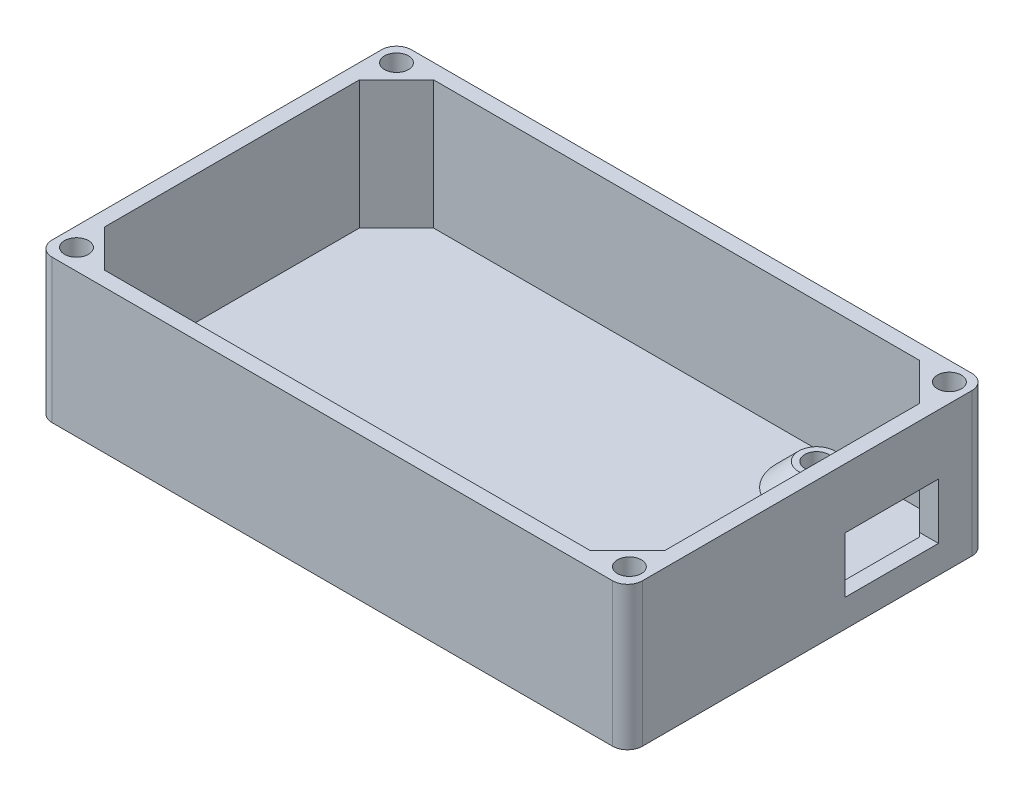
SolidWorks part; units mm, degrees
ref_plane "Front Plane" through (0, 0, 0) normal (0, 0, 1) x (1, 0, 0)
ref_plane "Top Plane" through (0, 0, 0) normal (0, 1, 0) x (1, 0, 0)
ref_plane "Right Plane" through (0, 0, 0) normal (1, 0, 0) x (0, 0, -1)
sketch "Sketch1" plane through (0, 0, 0) normal (0, 1, 0) x (1, 0, 0)
  line L0 (-1056.3053, 0) -> (48943.6947, 0) construction
  line L6 (27.9993, -24.5) -> (-50.8607, -24.5)
  line L8 (-7.0007, -998.7263) -> (-7.0007, 49001.2737) construction
  line L9 (27.9993, -24.5) -> (27.9993, 23.5)
  line L10 (27.9993, 23.5) -> (-50.8607, 23.5)
  line L11 (-50.8607, -24.5) -> (-50.8607, 23.5)
  line L12 (27.9993, -24.5) -> (-50.8607, 23.5) construction
  line L13 (27.9993, 23.5) -> (-50.8607, -24.5) construction
  point P0 (-7.0007, -0.5)
  dimension "D1" = 0.5
  dimension "D2" = 35
  dimension "D3" = 23.5
  dimension "D4" = 24.5
  dimension "D5" = 43.86
extrude "Boss-Extrude1" add sketch "Sketch1" along normal blind 18.15 and the other way blind 1
shell "Shell1" thickness 2 removed face at (-11.4307, 18.15, 0.5)
sketch "Sketch4" plane through (0, 1, 0) normal (0, 1, 0) x (1, 0, 0)
  line L0 (-50.8607, 23.5) -> (-50.8607, -24.5) construction
  line L1 (-50.8607, -24.5) -> (27.9993, -24.5) construction
  line L2 (27.9993, 23.5) -> (-50.8607, 23.5) construction
  circle A0 centre (-35.6907, -17.71) radius 2
  circle A1 centre (-4.7107, -11.75) radius 2
  circle A2 centre (11.6793, 17.1) radius 2
  dimension "D1" = 4
  dimension "D2" = 15.17
  dimension "D3" = 6.79
  dimension "D4" = 6.4
  dimension "D5" = 47.37
  dimension "D6" = 12.75
  dimension "D7" = 46.15
extrude "Boss-Extrude2" add sketch "Sketch4" against normal blind 4.4 from offset 3
chamfer "Chamfer2" distance 3.4 angle 45 1 edges at (-4.7107, 1, 13.75)
chamfer "Chamfer3" distance 3.4 angle 45 1 edges at (11.6793, 1, -15.1)
chamfer "Chamfer4" distance 3.4 angle 45 1 edges at (-35.6907, 1, 19.71)
sketch "Sketch9" plane through (0, 1, 0) normal (0, 1, 0) x (1, 0, 0)
  line L0 (-48.8607, -17.5358) -> (-48.8607, 16.5357) construction
  line L1 (-48.8607, 21.5) -> (-48.8607, -22.5) construction
  line L2 (-48.8607, 21.5) -> (-48.8607, -22.5) construction
  line L3 (-48.8607, 16.5357) -> (-43.8965, 21.5)
  line L4 (8.5488, 21.5) -> (-48.8607, 21.5) construction
  line L5 (-43.8965, 21.5) -> (21.035, 21.5) construction
  line L6 (25.9993, 21.5) -> (-48.8607, 21.5) construction
  line L7 (21.035, 21.5) -> (25.9993, 16.5358)
  line L9 (25.9993, 16.5358) -> (25.9993, -17.5358) construction
  line L10 (25.9993, -22.5) -> (25.9993, 21.5) construction
  line L11 (25.9993, -17.5358) -> (21.035, -22.5)
  line L13 (21.035, -22.5) -> (-43.8965, -22.5) construction
  line L14 (-48.8607, -22.5) -> (-38.1839, -22.5) construction
  line L15 (-43.8965, -22.5) -> (-48.8607, -17.5358)
  line L16 (-43.8965, 21.5) -> (-48.8607, 21.5)
  line L17 (-48.8607, 21.5) -> (-48.8607, 16.5357)
  line L18 (-48.8607, -17.5358) -> (-48.8607, -22.5)
  line L19 (-48.8607, -22.5) -> (-43.8965, -22.5)
  line L20 (21.035, -22.5) -> (25.9993, -22.5)
  line L21 (-48.8607, -22.5) -> (25.9993, -22.5) construction
  line L22 (25.9993, -22.5) -> (25.9993, -17.5358)
  line L23 (21.035, 21.5) -> (25.9993, 21.5)
  line L24 (25.9993, 21.5) -> (25.9993, 16.5358)
  dimension "D1" = 64.9315
extrude "Boss-Extrude4" add sketch "Sketch9" along normal blind 17.15
sketch "Sketch14" plane through (0, 18.15, 0) normal (0, 1, 0) x (1, 0, 0)
  line L0 (-1011.0006, -0.5) -> (48988.9994, -0.5) construction
  line L2 (-9.4307, -998.3868) -> (-9.4307, 49001.6132) construction
  line L5 (25.4993, -21.75) -> (-48.3607, -21.75) construction
  line L6 (25.4993, -21.75) -> (25.4993, 21) construction
  line L8 (25.4993, 21) -> (-48.3607, 21) construction
  line L9 (-48.3607, -21.75) -> (-48.3607, 21) construction
  line L10 (25.4993, -21.75) -> (-48.3607, 21) construction
  line L15 (25.4993, 21) -> (-48.3607, -21.75) construction
  circle A0 centre (-48.3607, 21) radius 1.6
  circle A1 centre (25.4993, 21) radius 1.6
  circle A2 centre (25.4993, -21.75) radius 1.6
  circle A3 centre (-48.3607, -21.75) radius 1.6
  point P8 (-9.4307, -0.5)
  dimension "D3" = 3.2
  dimension "D1" = 34.93
  dimension "D2" = 38.93
  dimension "D4" = 21.5
  dimension "D5" = 21.25
extrude "Cut-Extrude4" cut sketch "Sketch14" against normal blind 22 and the other way through all
fillet "Fillet1" radius 2 4 edges at (-50.8607, 8.575, 24.5) (-50.8607, 8.575, -23.5) (27.9993, 8.575, -23.5) (27.9993, 8.575, 24.5)
sketch "Sketch17" plane through (27.9993, 0, 0) normal (1, 0, 0) x (0, 0, -1)
  line L0 (-24.5, 18.15) -> (-24.5, -1) construction
  line L1 (4.53, 10.15) -> (17.04, 10.15)
  line L2 (4.53, 10.15) -> (4.53, 2.7)
  line L3 (4.53, 2.7) -> (17.04, 2.7)
  line L4 (17.04, 10.15) -> (17.04, 2.7)
  line L6 (-22.5, -1) -> (21.5, -1) construction
  dimension "D1" = 12.51
  dimension "D2" = 29.03
  dimension "D3" = 7.45
  dimension "D4" = 11.15
extrude "Cut-Extrude9" cut sketch "Sketch17" against normal up to next
sketch "Sketch21" plane through (0, 4, 0) normal (0, 1, 0) x (1, 0, 0)
  circle A0 centre (11.6793, 17.1) radius 1.6
  circle A1 centre (-4.7107, -11.75) radius 1.6
  circle A2 centre (-35.6907, -17.71) radius 1.6
extrude "Cut-Extrude10" cut sketch "Sketch21" against normal blind 4.2
